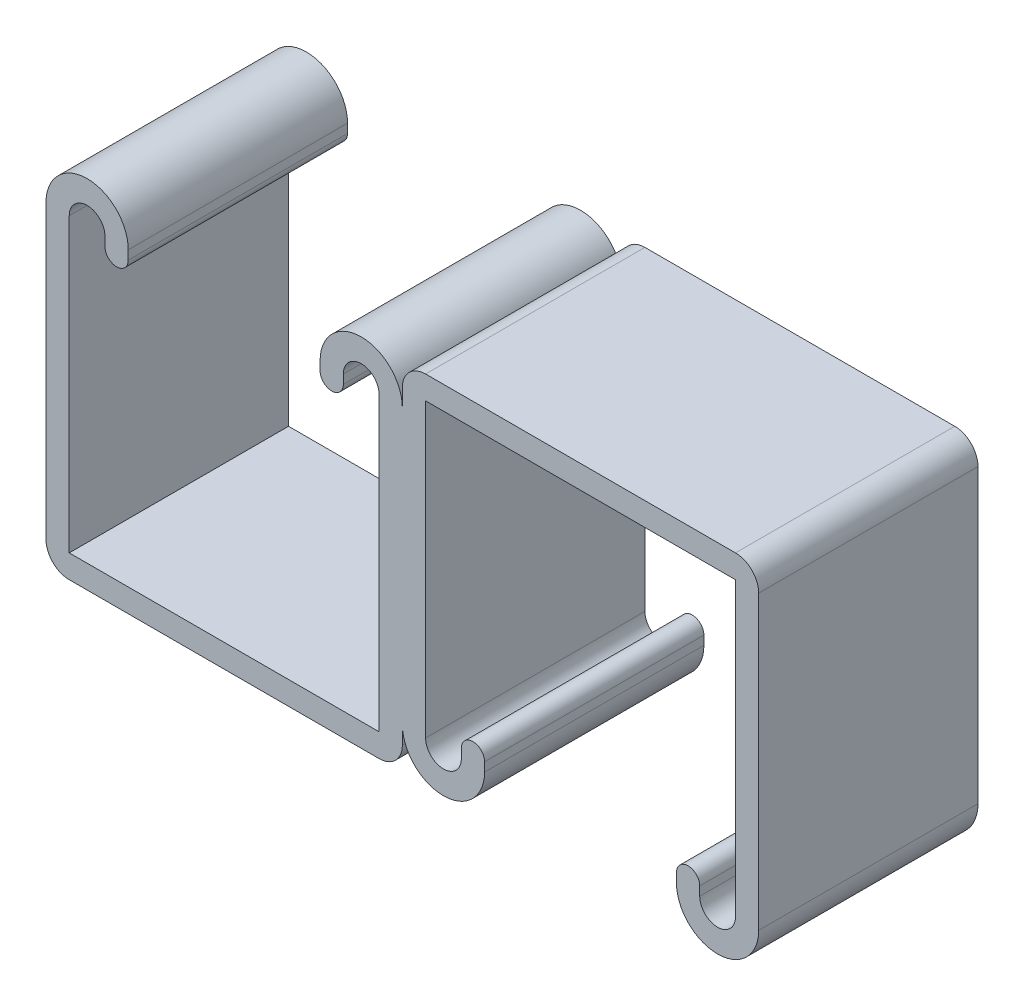
SolidWorks part; units mm, degrees
note: '?' marks a value the reader was unsure of.
ref_plane "Plane1" through (0, 0, 0) normal (0, 0, 1) x (1, 0, 0)
ref_plane "Plane2" through (0, 0, 0) normal (0, 1, 0) x (1, 0, 0)
ref_plane "Plane3" through (0, 0, 0) normal (1, 0, 0) x (0, 0, -1)
sketch "Sketch1" plane through (0, 0, 0) normal (0, 0, 1) x (1, 0, 0)
  line L0 (-41.275, 15.875) -> (-41.275, -17.9451)
  line L1 (-38.5826, -20.6375) -> (-2.6924, -20.6375)
  line L2 (0, -17.9451) -> (0, 15.875)
  line L3 (-9.525, 15.875) -> (-9.525, 14.8399)
  line L4 (-31.75, 15.875) -> (-31.75, 14.8399)
  line L5 (-34.4424, 15.875) -> (-34.4424, 14.8399)
  line L6 (-38.5826, 15.875) -> (-38.5826, -17.9451)
  line L7 (-38.5826, -17.9451) -> (-2.6924, -17.9451)
  line L8 (-2.6924, -17.9451) -> (-2.6924, 15.875)
  line L9 (-6.8326, 15.875) -> (-6.8326, 14.8399)
  line L10 (-44.483, 20.6375) -> (25.4, 20.6375) construction
  line L11 (-36.5125, 13.4937) -> (12.8524, 13.4937) construction
  arc A0 (0, 15.875) -> (-9.525, 15.875) centre (-4.7625, 15.875) ccw
  arc A1 (-41.275, 15.875) -> (-31.75, 15.875) centre (-36.5125, 15.875) cw
  arc A2 (-38.5826, -20.6375) -> (-41.275, -17.9451) centre (-38.5826, -17.9451) cw
  arc A3 (-2.6924, -20.6375) -> (0, -17.9451) centre (-2.6924, -17.9451) ccw
  arc A4 (-38.5826, 15.875) -> (-34.4424, 15.875) centre (-36.5125, 15.875) cw
  arc A5 (-2.6924, 15.875) -> (-6.8326, 15.875) centre (-4.7625, 15.875) ccw
  arc A6 (-9.525, 14.8399) -> (-6.8326, 14.8399) centre (-8.1788, 14.8399) ccw
  arc A7 (-31.75, 14.8399) -> (-34.4424, 14.8399) centre (-33.0962, 14.8399) cw
  dimension "D5" = 20.6375
  dimension "D6" = 9.525
  dimension "D7" = 22.225
  dimension "D8" = 20.6375
  dimension "D9" = 7.1437
extrude "Base-Extrude" add sketch "Sketch1" along normal mid plane 25.4
ref_axis "Axis1" through (0, 0, -50) along (0, 0, 1)?
pattern_circular "CirPattern1" count 2 every 180 about axis through (0, 0, 0) along (0, 0, 1) of "Base-Extrude"
equation "\"D7@Sketch1\" = \"Width@Sketch1\" - 2 * \"D6@Sketch1\""
equation "\"D1@Sketch1\" = \"gauge@Sketch1\""
